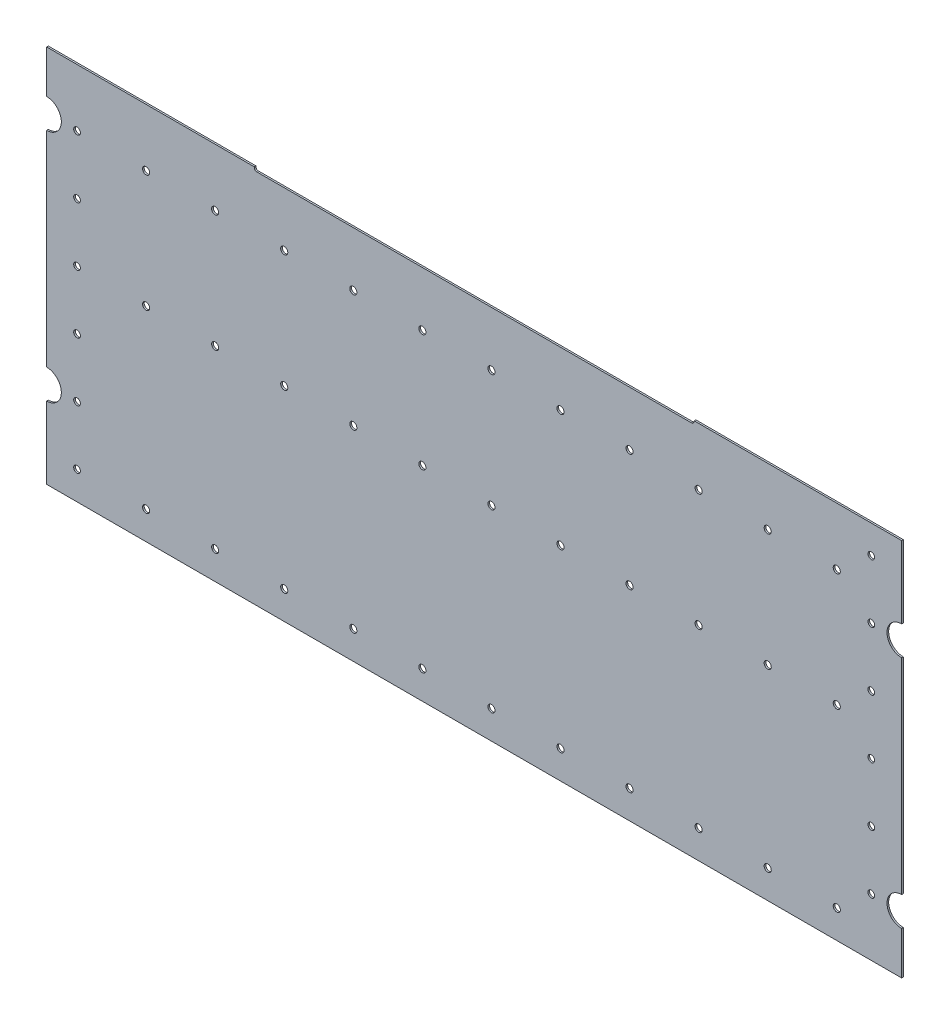
SolidWorks part; units mm, degrees
ref_plane "Plan de face" through (0, 0, 0) normal (0, 0, 1) x (1, 0, 0)
ref_plane "Plan de dessus" through (0, 0, 0) normal (0, 1, 0) x (1, 0, 0)
ref_plane "Plan de droite" through (0, 0, 0) normal (1, 0, 0) x (0, 0, -1)
sketch "Esquisse2" plane through (0, 0, 0) normal (0, 0, 1) x (1, 0, 0)
  line L1 (-204.75, -91) -> (204.75, -91)
  line L2 (-204.75, -91) -> (-204.75, 91)
  line L3 (-204.75, 91) -> (204.75, 91)
  line L4 (204.75, -91) -> (204.75, 91)
  line L5 (-204.75, -91) -> (204.75, 91) construction
  line L6 (-204.75, 91) -> (204.75, -91) construction
  point P0 (0, 0)
  dimension "D1" = 182
  dimension "D2" = 409.5
extrude "Boss.-Extru.2" add sketch "Esquisse2" along normal blind 0.7937
sketch "Esquisse3" plane through (0, 0, 0.7937) normal (0, 0, 1) x (1, 0, 0)
  line L0 (-204.75, -91) -> (204.75, -91) construction
  line L1 (204.75, 91) -> (-204.75, 91) construction
  line L2 (-204.75, 91) -> (-204.75, -91) construction
  circle A0 centre (-156.75, 63) radius 1.7
  circle A1 centre (-156.75, 7) radius 1.7
  circle A2 centre (-156.75, -77) radius 1.7
  dimension "D1" = 3.4
  dimension "D2" = 14
  dimension "D3" = 28
  dimension "D4" = 48
  dimension "D5" = 48
  dimension "D6" = 84
extrude "Enlèv. mat.-Extru.1" cut sketch "Esquisse3" against normal through all
pattern_linear "Répétition linéaire1" count 11 spacing 33 along (1, 0, 0) of "Enlèv. mat.-Extru.1"
sketch "Esquisse4" plane through (0, 0, 0) normal (0, 0, -1) x (-1, 0, 0)
  line L0 (-204.75, 91) -> (204.75, 91) construction
  line L1 (-105, 91) -> (105, 91)
  line L2 (-105, 91) -> (-105, 89)
  line L3 (-105, 89) -> (105, 89)
  line L4 (105, 91) -> (105, 89)
  point P6 (0, 89)
  dimension "D1" = 210
  dimension "D2" = 2
extrude "Enlèv. mat.-Extru.2" cut sketch "Esquisse4" against normal through all
fillet "Congé1" radius 1 4 edges at (-105, 89, 0.3969) (-105, 91, 0.3969) (105, 89, 0.3969) (105, 91, 0.3969)
sketch "Esquisse5" plane through (0, 0, 0) normal (0, 0, -1) x (-1, 0, 0)
  line L0 (106, 91) -> (204.75, 91) construction
  line L1 (-204.25, -90.5) -> (204.25, -90.5)
  line L2 (-204.25, -90.5) -> (-204.25, 90.5)
  line L3 (-204.25, 90.5) -> (204.25, 90.5)
  line L4 (204.25, -90.5) -> (204.25, 90.5)
  line L5 (-204.25, -90.5) -> (204.25, 90.5) construction
  line L6 (-204.25, 90.5) -> (204.25, -90.5) construction
  line L7 (204.75, 91) -> (204.75, -91) construction
  point P0 (0, 0)
  dimension "D1" = 0.5
  dimension "D2" = 0.5
extrude "Enlèv. mat.-Extru.3" cut sketch "Esquisse5" against normal through all flip side to cut
hole_wizard "Dégagement M31" positions "Esquisse8" profile "Esquisse7" hole size "M3" standard "Ansi Metric" end condition through all
sketch "Esquisse8" plane through (0, 0, 0) normal (0, 0, -1) x (-1, 0, 0)
  point P0 (-189.75, 77)
  point P3 (-189.75, 49)
  point P6 (-189.75, 21)
  point P9 (-189.75, -7)
  point P12 (-189.75, -35)
  point P15 (-189.75, -63)
  point P18 (189.75, 63)
  point P21 (189.75, 35)
  point P24 (189.75, 7)
  point P27 (189.75, -21)
  point P30 (189.75, -49)
  point P33 (189.75, -77)
sketch "Esquisse7" plane through (189.75, 77, 0) normal (1, 0, 0) x (0, 1, 0)
  line L0 (0, 0) -> (0, 0.7937)
  line L1 (0, 0.7937) -> (1.6, 0.7937)
  line L2 (1.6, 0.7937) -> (1.6, 0)
  line L5 (1.6, 0) -> (0, 0)
  line L11 (0, -6.35) -> (0, 107.95) construction
  dimension "Diamètre du perçage jusqu'au prochain" = 3.2
  dimension "Profondeur du perçage jusqu'au prochain" = 0.7937
sketch "Esquisse14" plane through (0, 0, 0) normal (0, 0, -1) x (-1, 0, 0)
  line L0 (-204.25, 90.5) -> (-204.25, -90.5) construction
  line L1 (-105.134, 90.5) -> (-204.25, 90.5) construction
  line L2 (-204.25, -90.5) -> (204.25, -90.5) construction
  line L3 (-204.25, -56) -> (-204.25, -70)
  line L4 (-204.25, 56) -> (-204.25, 42)
  line L5 (204.25, -90.5) -> (204.25, 90.5) construction
  line L6 (204.25, 90.5) -> (105.134, 90.5) construction
  line L7 (204.25, 70) -> (204.25, 56)
  line L8 (204.25, -42) -> (204.25, -56)
  arc A0 (-204.25, 42) -> (-204.25, 56) centre (-204.25, 49) ccw
  arc A1 (-204.25, -70) -> (-204.25, -56) centre (-204.25, -63) ccw
  arc A2 (204.25, 70) -> (204.25, 56) centre (204.25, 63) ccw
  arc A3 (204.25, -42) -> (204.25, -56) centre (204.25, -49) ccw
  dimension "D2" = 14
  dimension "D1" = 41.5
  dimension "D3" = 27.5
  dimension "D4" = 27.5
  dimension "D5" = 41.5
extrude "Enlèv. mat.-Extru.4" cut sketch "Esquisse14" against normal up to next contours A0 L4 | A1 L3 | A3 L8 | A2 L7
